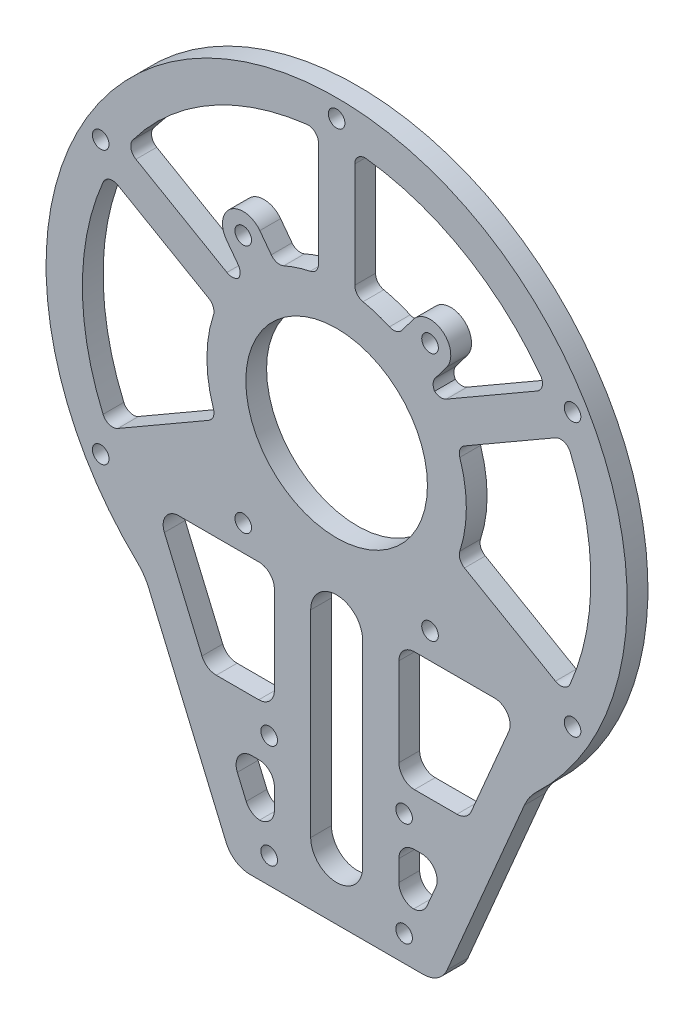
SolidWorks part; units mm, degrees
ref_plane "前视基准面" through (0, 0, 0) normal (0, 0, 1) x (1, 0, 0)
ref_plane "上视基准面" through (0, 0, 0) normal (0, 1, 0) x (1, 0, 0)
ref_plane "右视基准面" through (0, 0, 0) normal (1, 0, 0) x (0, 0, -1)
other "Configuration Table"
sketch "草图1" plane through (0, 0, 0) normal (0, 0, 1) x (1, 0, 0)
  line L0 (-31.5, -42) -> (31.5, -42)
  line L1 (-18, 24) -> (18, 24) construction
  line L2 (-18, 24) -> (-18, -24) construction
  line L3 (-18, -24) -> (18, -24) construction
  line L4 (18, 24) -> (18, -24) construction
  line L5 (-18, 24) -> (18, -24) construction
  line L6 (-18, -24) -> (18, 24) construction
  line L7 (-37.0405, -42) -> (37.0405, -42)
  line L8 (0, 0) -> (0, -106.2402) construction
  line L9 (-20, -42) -> (-20, -82)
  line L10 (-20, -82) -> (20, -82)
  line L11 (0, -82) -> (0, -42)
  line L12 (-37.0405, -42) -> (-20, -82)
  line L13 (37.0405, -42) -> (20, -82)
  line L14 (20, -42) -> (20, -82)
  circle A0 centre (-18, 24) radius 1.6
  circle A1 centre (18, 24) radius 1.6
  circle A2 centre (18, -24) radius 1.6
  circle A3 centre (-18, -24) radius 1.6
  circle A4 centre (0, 0) radius 52.5 construction
  circle A5 centre (0, 52.5) radius 1.6
  circle A6 centre (45.4663, 26.25) radius 1.6
  circle A7 centre (45.4663, -26.25) radius 1.6
  circle A8 centre (0, -52.5) radius 1.6
  circle A9 centre (-45.4663, -26.25) radius 1.6
  circle A10 centre (-45.4663, 26.25) radius 1.6
  circle A11 centre (0, 0) radius 56
  point P0 (0, 0)
  point P26 (0, 0)
  point P33 (0, -106.2402)
  dimension "D3" = 3.2
  dimension "D4" = 3.2
  dimension "D5" = 3.2
  dimension "D6" = 3.2
  dimension "D7" = 105
  dimension "D8" = 3.2
  dimension "D11" = 112
  dimension "D1" = 48
  dimension "D2" = 36
  dimension "D10" = 18
  dimension "D12" = 20
  dimension "D13" = 40
  dimension "D9" = 6
extrude "凸台-拉伸1" add sketch "草图1" along normal blind 4 contours L7 A11 L0 A0 A1 A2 A3 A5 A6 A7 A9 A10 | A11 L14 L13 | L14 A11 L7 | L11 A11 L14 L0 A8 | A11 L11 L10 L14 | A11 L9 L10 L11 | L9 A11 L11 A8 L7 | A11 L12 L9 | L7 A11 L9 L0 | L11 A8 | L11 A8 region at (0, 3.6893, 0) region at (-26.0403, -45.6765, 0) region at (-9.6632, -48.3749, 0) region at (-25.5313, -59.3255, 0) region at (9.6632, -48.3749, 0) region at (-10.2246, -68.3708, 0) region at (26.0403, -45.6765, 0) region at (0.6791, -52.5, 0) region at (-0.6791, -52.5, 0) region at (10.2246, -68.3708, 0) region at (25.5313, -59.3255, 0)
fillet "圆角1" radius 10 2 edges at (37.0405, -42, 2) (-37.0405, -42, 2)
fillet "圆角2" radius 5 2 edges at (20, -82, 2) (-20, -82, 2)
sketch "草图2" plane through (0, 0, 4) normal (0, 0, 1) x (1, 0, 0)
  line L0 (0, 0) -> (0, 52.5) construction
  line L1 (0, 0) -> (56, 0) construction
  line L2 (-3.5, 52.5) -> (-3.5, 24.7538)
  line L3 (3.5, 52.5) -> (3.5, 24.7538)
  line L4 (47.2163, 23.2189) -> (23.1874, 9.3458)
  line L5 (43.7163, 29.2811) -> (19.6874, 15.408)
  line L6 (43.7163, -29.2811) -> (19.6874, -15.408)
  line L7 (47.2163, -23.2189) -> (23.1874, -9.3458)
  line L8 (-3.5, -52.5) -> (-3.5, -24.7538) [skipped]
  line L9 (3.5, -52.5) -> (3.5, -24.7538) [skipped]
  line L10 (-47.2163, -23.2189) -> (-23.1874, -9.3458)
  line L11 (-43.7163, -29.2811) -> (-19.6874, -15.408)
  line L12 (-43.7163, 29.2811) -> (-19.6874, 15.408)
  line L13 (-47.2163, 23.2189) -> (-23.1874, 9.3458)
  line L14 (-18, 24) -> (0, 0) construction
  line L15 (-21.2, 21.6) -> (-18.0068, 17.3423)
  line L16 (-14.8, 26.4) -> (-11.6068, 22.1423)
  line L17 (18, 24) -> (0, 0) construction
  line L18 (0, 0) -> (18, -24) construction
  line L19 (-18, -24) -> (0, 0) construction
  line L20 (14.8, 26.4) -> (11.6068, 22.1423)
  line L21 (21.2, 21.6) -> (18.0068, 17.3423)
  line L22 (-21.2, -21.6) -> (-18.0068, -17.3423)
  line L23 (-14.8, -26.4) -> (-11.6068, -22.1423)
  line L24 (0, 0) -> (0, -82) construction
  line L25 (14.8, -26.4) -> (11.6068, -22.1423)
  line L26 (21.2, -21.6) -> (18.0068, -17.3423)
  line L27 (-16.6953, -82) -> (16.6953, -82) construction
  line L28 (-13, -82) -> (-13, -40.0117) construction
  line L29 (13, -82) -> (13, -40.0117) construction
  line L30 (0, -32) -> (0, -70) construction
  line L31 (5, -32) -> (5, -70)
  line L32 (-5, -32) -> (-5, -70)
  circle A0 centre (0, 52.5) radius 3.5
  arc A1 (38.5137, -40.6533) -> (-38.5137, -40.6533) centre (0, 0) ccw construction
  circle A2 centre (0, 0) radius 25
  circle A3 centre (0, 0) radius 25
  circle A4 centre (45.4663, 26.25) radius 3.5
  circle A5 centre (0, 0) radius 25
  circle A6 centre (45.4663, -26.25) radius 3.5
  circle A7 centre (0, 0) radius 25 [skipped]
  circle A8 centre (0, -52.5) radius 3.5 [skipped]
  circle A9 centre (0, 0) radius 25
  circle A10 centre (-45.4663, -26.25) radius 3.5
  circle A11 centre (0, 0) radius 25
  circle A12 centre (-45.4663, 26.25) radius 3.5
  circle A13 centre (-18, 24) radius 4
  circle A14 centre (-18, -24) radius 4
  circle A15 centre (18, -24) radius 4
  circle A16 centre (18, 24) radius 4
  circle A17 centre (-13, -77) radius 1.6
  circle A18 centre (-13, -57) radius 1.6
  circle A19 centre (13, -57) radius 1.6
  circle A20 centre (13, -77) radius 1.6
  arc A21 (5, -32) -> (-5, -32) centre (0, -32) ccw
  arc A22 (-5, -70) -> (5, -70) centre (0, -70) ccw
  circle A23 centre (0, 0) radius 49
  point P52 (0, 0)
  point P96 (0, -51)
  dimension "D1" = 50
  dimension "D2" = 7
  dimension "D4" = 8
  dimension "D5" = 8
  dimension "D6" = 8
  dimension "D7" = 8
  dimension "D8" = 3.2
  dimension "D9" = 3.2
  dimension "D10" = 20
  dimension "D11" = 5
  dimension "D13" = 5
  dimension "D15" = 12
  dimension "D16" = 98
  dimension "D3" = 6
  dimension "D12" = 13
  dimension "D14" = 32
extrude "切除-拉伸3" cut sketch "草图2" against normal blind 10 contours L32 A23 L31 A21 | A23 L32 A22 L31 | L13 A23 L10 A2 | L2 A23 L12 A2 L15 A13 L16 | L7 A23 L4 A2 | L5 A23 L3 A2 L20 A16 L21 | A18 | A19 | A20 | A17 region at (-18.8142, 33.2467, 4) region at (18.8142, 33.2467, 4) region at (-37.3901, 0, 4) region at (37.3901, 0, 4) region at (0, -63.4315, 4) region at (-4.2311, -39.1577, 4) region at (0, -38.1979, 4) region at (4.2311, -39.1577, 4) region at (-13, -77, 4) region at (-13, -57, 4) region at (13, -57, 4) region at (13, -77, 4) body kept at (-21.2952, -78.9596, 0)
sketch "草图3" plane through (0, 0, 0) normal (0, 0, -1) x (-1, 0, 0)
  circle A0 centre (0, 0) radius 17.5
  dimension "D1" = 35
extrude "切除-拉伸4" cut sketch "草图3" against normal blind 10
fillet "圆角3" radius 2 20 edges at (-3.5, 24.7538, 2) (-11.6068, 22.1423, 2) (-18.0068, 17.3423, 2) (-19.6874, 15.408, 2) (-40.5769, 27.4685, 2) (-3.5, 48.8748, 2) (11.6068, 22.1423, 2) (3.5, 24.7538, 2) (3.5, 48.8748, 2) (40.5769, 27.4685, 2) (23.1874, -9.3458, 2) (23.1874, 9.3458, 2) (44.0769, 21.4063, 2) (44.0769, -21.4063, 2) (-23.1874, 9.3458, 2) (-23.1874, -9.3458, 2) (-44.0769, -21.4063, 2) (-44.0769, 21.4063, 2) (19.6874, 15.408, 2) (18.0068, 17.3423, 2)
sketch "草图4" plane through (0, 0, 4) normal (0, 0, 1) x (1, 0, 0)
  line L0 (0, 0) -> (0, -82) construction
  line L1 (-16.6953, -82) -> (16.6953, -82) construction
  line L2 (12, -29) -> (12, -52)
  line L3 (12, -52) -> (25.1717, -52)
  line L4 (25.1717, -52) -> (34.97, -29)
  line L5 (34.97, -29) -> (12, -29)
  line L6 (5, -32) -> (5, -70) construction
  line L7 (36.1912, -43.9935) -> (21.2952, -78.9596) construction
  line L8 (-34.97, -29) -> (-12, -29)
  line L9 (-25.1717, -52) -> (-34.97, -29)
  line L10 (-12, -52) -> (-25.1717, -52)
  line L11 (-12, -29) -> (-12, -52)
  line L12 (12, -52) -> (12, -82) construction
  line L13 (12, -62) -> (20.9115, -62)
  line L14 (20.9115, -62) -> (16.6514, -72)
  line L15 (16.6514, -72) -> (12, -72)
  line L16 (12, -72) -> (12, -62)
  line L17 (-12, -52) -> (-12, -82) construction
  line L18 (-12, -72) -> (-12, -62)
  line L19 (-16.6514, -72) -> (-12, -72)
  line L20 (-20.9115, -62) -> (-16.6514, -72)
  line L21 (-12, -62) -> (-20.9115, -62)
  circle A0 centre (18, -24) radius 1.6 construction
  circle A1 centre (13, -57) radius 1.6 construction
  circle A2 centre (13, -77) radius 1.6 construction
  dimension "D1" = 5
  dimension "D2" = 5
  dimension "D3" = 7
  dimension "D4" = 7
  dimension "D5" = 5
  dimension "D6" = 5
  dimension "D7" = 7
extrude "切除-拉伸5" cut sketch "草图4" against normal blind 10
fillet "圆角4" radius 3 16 edges at (25.1717, -52, 2) (12, -52, 2) (12, -29, 2) (34.97, -29, 2) (-20.9115, -62, 2) (-12, -62, 2) (-12, -72, 2) (-16.6514, -72, 2) (20.9115, -62, 2) (16.6514, -72, 2) (12, -72, 2) (12, -62, 2) (-12, -29, 2) (-12, -52, 2) (-34.97, -29, 2) (-25.1717, -52, 2)
